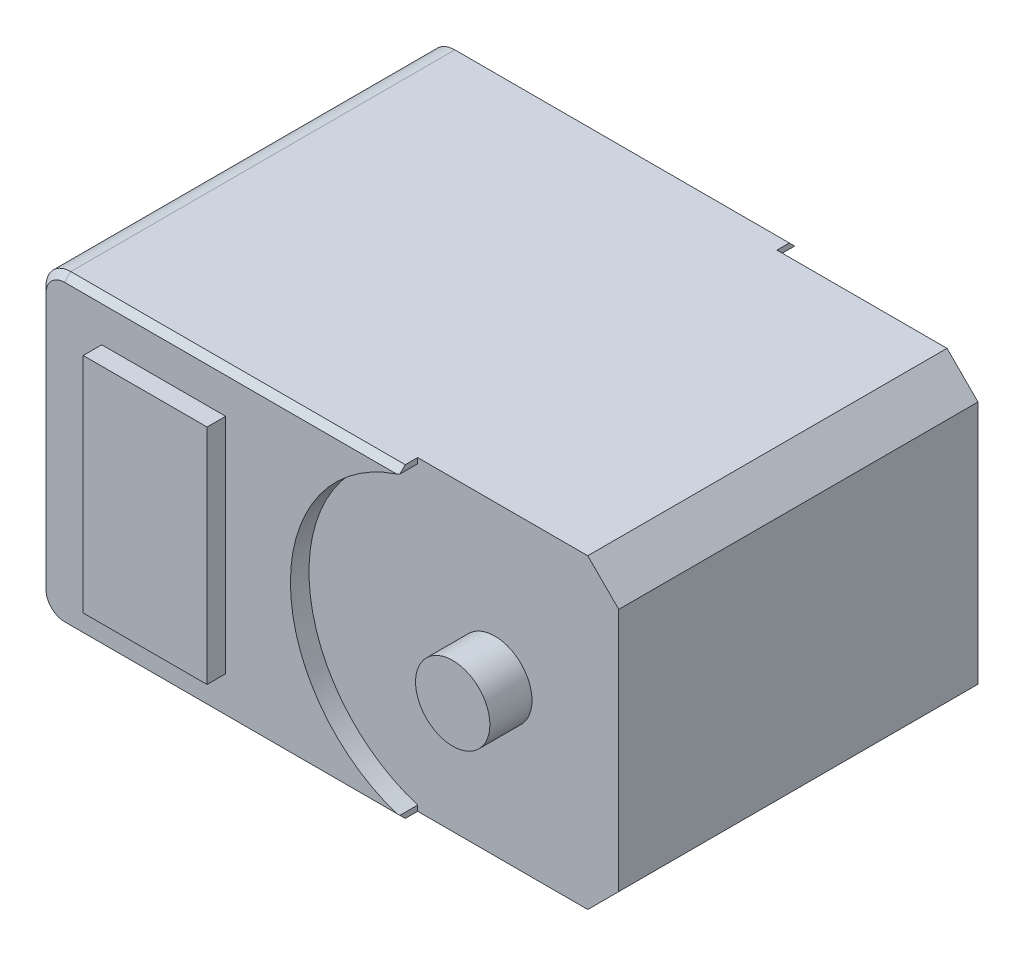
SolidWorks part; units mm, degrees
material "舵机材料"
ref_plane "前视基准面" through (0, 0, 0) normal (0, 0, 1) x (1, 0, 0)
ref_plane "上视基准面" through (0, 0, 0) normal (0, 1, 0) x (1, 0, 0)
ref_plane "右视基准面" through (0, 0, 0) normal (1, 0, 0) x (0, 0, -1)
other "Configuration Table"
sketch "草图1" plane through (0, 0, 0) normal (0, 0, 1) x (1, 0, 0)
  line L1 (0, 0) -> (45.23, 0)
  line L2 (0, 0) -> (0, 24.73)
  line L3 (0, 24.73) -> (45.23, 24.73)
  line L4 (45.23, 0) -> (45.23, 24.73)
  dimension "D1" = 45.23
  dimension "D2" = 24.73
extrude "凸台-拉伸1" add sketch "草图1" along normal blind 35
sketch "草图2" plane through (0, 0, 0) normal (0, 0, 1) x (1, 0, 0)
  line L1 (45.23, 24.73) -> (30.8978, 24.73)
  line L2 (45.23, 24.73) -> (45.23, 0)
  line L3 (45.23, 0) -> (30.8978, 0)
  line L9 (0, 24.73) -> (0, 0)
  line L10 (0, 0) -> (45.23, 0)
  line L11 (45.23, 0) -> (45.23, 24.73)
  line L12 (45.23, 24.73) -> (0, 24.73)
  line L14 (30.8978, 0) -> (45.23, 0)
  line L15 (45.23, 0) -> (45.23, 24.73)
  line L16 (45.23, 24.73) -> (30.8978, 24.73)
  arc A0 (30.8978, 24.73) -> (30.8978, 0) centre (32.73, 12.365) ccw
  dimension "D2" = 0
extrude "切除-拉伸1" cut sketch "草图2" along normal blind 3 contours L1 A0 L3 L2 region at (33.867, 12.365, 0)
sketch "草图5" plane through (0, 0, 0) normal (0, 0, 1) x (1, 0, 0)
  line L0 (30.8978, 24.73) -> (0, 24.73) construction
  line L2 (0, 0) -> (0, 24.73)
  line L4 (29, 0) -> (29, 24.73)
  line L5 (30.8978, 0) -> (30.8978, 24.73)
  line L14 (30.8978, 24.73) -> (0, 24.73)
  line L15 (0, 0) -> (30.8978, 0)
  line L16 (0, 24.73) -> (0, 0)
  line L17 (30.8978, 24.73) -> (29, 24.73)
  line L18 (29, 0) -> (30.8978, 0)
  line L19 (0, 24.73) -> (0, 0)
  arc A4 (30.8978, 24.73) -> (30.8978, 0) centre (32.73, 12.365) ccw
  dimension "D1" = 29
  dimension "D3" = 0
extrude "切除-拉伸3" cut sketch "草图5" along normal up to surface (3 mm away) contours L4 L18 L5 L17 region at (29.5901, 0.137, 0) region at (29.5901, 24.593, 0) region at (29.9546, 12.365, 0) up to face at (35.397, 12.365, 3)
ref_plane "基准面1" through (0, 0, 17.5) normal (0, 0, 1) x (1, 0, 0)
mirror "镜向1" about plane through (0, 0, 17.5) normal (0, 0, 1) of "切除-拉伸3", "切除-拉伸1"
sketch "草图3" plane through (0, 0, 0) normal (0, 0, 1) x (1, 0, 0)
  arc A0 (29, 24.2955) -> (29, 0.4345) centre (32.73, 12.365) ccw construction
  arc A1 (29, 24.2955) -> (29, 0.4345) centre (32.73, 12.365) ccw
  circle A3 centre (35.23, 12.365) radius 3
  point P4 (0, 0)
  dimension "D1" = 6
  dimension "D2" = 2.5
extrude "凸台-拉伸2" add sketch "草图3" along normal blind 17.9 and the other way blind 18.6 from surface contours A3 region at (35.23, 12.365, 0) starting at plane "基准面1"
sketch "草图4" plane through (0, 0, 0) normal (0, 0, 1) x (1, 0, 0)
  line L0 (0, 12.365) -> (51.1364, 12.365) construction
  line L1 (0, 24.73) -> (30.8978, 24.73)
  line L2 (0, 24.73) -> (0, 19.73)
  line L3 (0, 19.73) -> (30.8978, 19.73)
  line L4 (30.8978, 24.73) -> (30.8978, 19.73)
  line L5 (0, 24.73) -> (0, 0) construction
  line L6 (30.8978, 0) -> (30.8978, 5)
  line L7 (0, 0) -> (0, 5)
  line L8 (0, 0) -> (30.8978, 0)
  line L9 (0, 5) -> (30.8978, 5)
  dimension "D1" = 5
extrude "切除-拉伸2" cut sketch "草图4" along normal blind 1.5
chamfer "倒角1" distance 2.5 angle 45 2 edges at (45.23, 24.73, 17.5) (45.23, 0, 17.5)
fillet "圆角1" radius 2 2 edges at (0, 24.73, 18.25) (0, 0, 18.25)
sketch "草图6" plane through (0, 0, 35) normal (0, 0, 1) x (1, 0, 0)
  line L0 (-50.6859, 12.365) -> (-40.6859, 12.365) construction
  line L2 (0, 22.73) -> (0, 2) construction
  line L3 (5, 21.365) -> (15, 21.365)
  line L4 (5, 21.365) -> (5, 3.365)
  line L5 (5, 3.365) -> (15, 3.365)
  line L6 (15, 21.365) -> (15, 3.365)
  line L12 (29, 24.73) -> (2, 24.73)
  line L13 (0, 22.73) -> (0, 2)
  line L14 (2, 0) -> (29, 0)
  line L15 (29, 0) -> (29, 0.4345)
  line L16 (29, 24.2955) -> (29, 24.73)
  line L17 (29, 24.73) -> (2, 24.73)
  line L18 (0, 22.73) -> (0, 2)
  line L19 (2, 0) -> (29, 0)
  line L20 (29, 0) -> (29, 0.4345)
  line L21 (29, 24.2955) -> (29, 24.73)
  arc A3 (2, 24.73) -> (0, 22.73) centre (2, 22.73) ccw
  arc A5 (29, 24.2955) -> (29, 0.4345) centre (32.73, 12.365) ccw
  arc A8 (29, 24.2955) -> (29, 0.4345) centre (32.73, 12.365) ccw
  arc A9 (2, 24.73) -> (0, 22.73) centre (2, 22.73) ccw
  arc A10 (0, 2) -> (2, 0) centre (2, 2) ccw
  arc A11 (0, 2) -> (2, 0) centre (2, 2) ccw
  point P3 (-45.6859, 12.365)
  dimension "D1" = 9
  dimension "D2" = 0
  dimension "D3" = 5
  dimension "D4" = 10
extrude "切除-拉伸4" cut sketch "草图6" against normal blind 1.5
chamfer "倒角2" distance 0.5 angle 45 12 edges at (0, 21.23, 1.5) (0.5858, 24.1442, 1.5) (15.5, 24.73, 1.5) (0, 12.365, 0) (0, 3.5, 1.5) (0.5858, 0.5858, 1.5) (15.5, 0, 1.5) (15.5, 24.73, 33.5) (0.5858, 24.1442, 33.5) (0, 12.365, 33.5) (0.5858, 0.5858, 33.5) (15.5, 0, 33.5)
